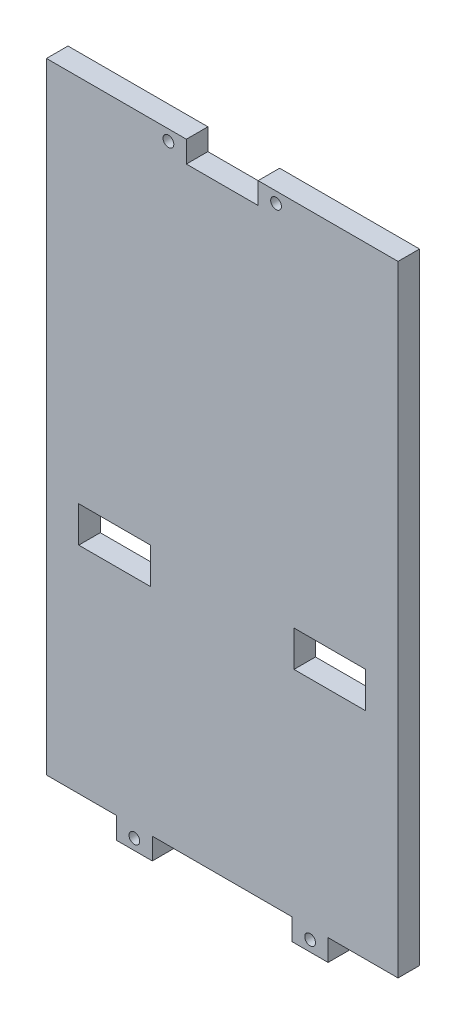
SolidWorks part; units mm, degrees
ref_plane "Plan de face" through (0, 0, 0) normal (0, 0, 1) x (1, 0, 0)
ref_plane "Plan de dessus" through (0, 0, 0) normal (0, 1, 0) x (1, 0, 0)
ref_plane "Plan de droite" through (0, 0, 0) normal (1, 0, 0) x (0, 0, -1)
sketch "Esquisse1" plane through (0, 0, 0) normal (0, 0, 1) x (1, 0, 0)
  line L0 (0, 176.8395) -> (0, -221.1538) construction
  line L1 (-49, 86.5) -> (49, 86.5)
  line L2 (-49, 86.5) -> (-49, -86.5)
  line L3 (-49, -86.5) -> (49, -86.5)
  line L4 (49, 86.5) -> (49, -86.5)
  line L5 (376.8436, 0) -> (-286.1998, 0) construction
  line L6 (-376.8436, 0) -> (286.1998, 0) construction
  line L7 (20, -16.5) -> (20, -26.5)
  line L8 (-40, -16.5) -> (-20, -16.5)
  line L9 (-40, -16.5) -> (-40, -26.5)
  line L10 (-40, -26.5) -> (-20, -26.5)
  line L11 (-20, -16.5) -> (-20, -26.5)
  line L12 (40, -26.5) -> (20, -26.5)
  line L13 (40, -16.5) -> (40, -26.5)
  line L14 (40, -16.5) -> (20, -16.5)
  dimension "D1" = 173
  dimension "D2" = 98
  dimension "D3" = 49
  dimension "D4" = 86.5
  dimension "D5" = 10
  dimension "D6" = 20
  dimension "D7" = 60
  dimension "D8" = 9
extrude "Boss.-Extru.1" add sketch "Esquisse1" along normal blind 6
sketch "Esquisse2" plane through (0, 0, 6) normal (0, 0, 1) x (1, 0, 0)
  line L1 (-49, -86.5) -> (49, -86.5) construction
  line L2 (29.5, -86.5) -> (19.5, -86.5)
  line L3 (29.5, -86.5) -> (29.5, -92.5)
  line L4 (29.5, -92.5) -> (19.5, -92.5)
  line L6 (154.6429, 0) -> (-167.6281, 0) construction
  line L7 (19.5, -86.5) -> (19.5, -92.5)
  line L8 (-49, 86.5) -> (-49, -86.5) construction
  line L9 (-19.5, -86.5) -> (-29.5, -86.5)
  line L10 (-19.5, -86.5) -> (-19.5, -92.5)
  line L11 (-19.5, -92.5) -> (-29.5, -92.5)
  line L12 (-29.5, -86.5) -> (-29.5, -92.5)
  dimension "D1" = 6
  dimension "D2" = 6
  dimension "D3" = 10
  dimension "D4" = 10
  dimension "D5" = 19.5
  dimension "D6" = 39
extrude "Boss.-Extru.2" add sketch "Esquisse2" against normal blind 6
sketch "Esquisse3" plane through (0, 0, 6) normal (0, 0, 1) x (1, 0, 0)
  line L0 (-49, 86.5) -> (-49, -86.5) construction
  line L1 (55.0284, -89.5) -> (-66.8616, -89.5) construction
  line L2 (84.5882, 83.5) -> (-34.9143, 83.5) construction
  line L3 (19.5, -92.5) -> (29.5, -92.5) construction
  line L4 (49, -86.5) -> (49, 86.5) construction
  line L5 (49, 86.5) -> (-49, 86.5) construction
  line L6 (-29.5, -86.5) -> (-29.5, -92.5) construction
  line L7 (19.5, -86.5) -> (19.5, -92.5) construction
  circle A0 centre (-15, 83.5) radius 1.5
  circle A1 centre (24.5, -89.5) radius 1.5
  circle A2 centre (-24.5, -89.5) radius 1.5
  circle A3 centre (15, 83.5) radius 1.5
  dimension "D1" = 3
  dimension "D2" = 3
  dimension "D3" = 34
  dimension "D4" = 34
  dimension "D7" = 3
  dimension "D8" = 3
  dimension "D9" = 5
  dimension "D10" = 5
  dimension "D5" = 3
  dimension "D6" = 3
extrude "Enlèv. mat.-Extru.1" cut sketch "Esquisse3" against normal blind 6
sketch "Esquisse4" plane through (0, 0, 6) normal (0, 0, 1) x (1, 0, 0)
  line L0 (49, 86.5) -> (-49, 86.5) construction
  line L1 (-10, 86.5) -> (10, 86.5)
  line L2 (-10, 86.5) -> (-10, 80.5)
  line L3 (-10, 80.5) -> (10, 80.5)
  line L4 (10, 86.5) -> (10, 80.5)
  line L5 (49, -86.5) -> (49, 86.5) construction
  dimension "D1" = 6
  dimension "D2" = 20
  dimension "D3" = 39
extrude "Enlèv. mat.-Extru.2" cut sketch "Esquisse4" against normal blind 6
equation "\"D3@Esquisse1\"=\"D2@Esquisse1\"/2"
equation "\"D4@Esquisse1\"=\"D1@Esquisse1\"/2"
